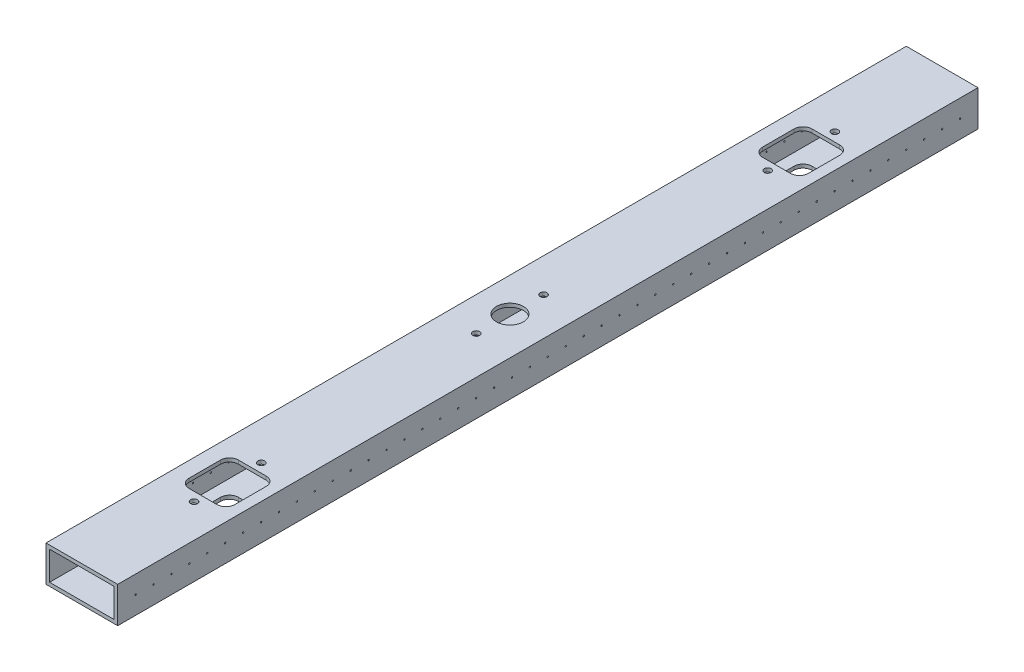
SolidWorks part; units mm, degrees
note: The reader was unsure of these and kept them because the rebuilt part matched: shared geometry of "Sketch2<9>".
ref_plane "Front Plane" through (0, 0, 0) normal (0, 0, 1) x (1, 0, 0)
ref_plane "Top Plane" through (0, 0, 0) normal (0, 1, 0) x (1, 0, 0)
ref_plane "Right Plane" through (0, 0, 0) normal (1, 0, 0) x (0, 0, -1)
sketch "Sketch1" plane through (0, 0, 0) normal (0, 0, 1) x (1, 0, 0)
  line L0 (2.54, -2.54) -> (2.54, -22.86)
  line L1 (0, 0) -> (50.8, 0)
  line L2 (0, 0) -> (0, -25.4)
  line L3 (0, -25.4) -> (50.8, -25.4)
  line L4 (50.8, 0) -> (50.8, -25.4)
  line L5 (2.54, -22.86) -> (48.26, -22.86)
  line L6 (48.26, -2.54) -> (48.26, -22.86)
  line L7 (2.54, -2.54) -> (48.26, -2.54)
  dimension "D1" = 50.8
  dimension "D2" = 25.4
  dimension "D3" = 2.54
extrude "Boss-Extrude1" add sketch "Sketch1" along normal blind 609.6
sketch "Sketch2" plane through (0, 0, 0) normal (0, 1, 0) x (1, 0, 0)
  line L0 (27.124, 0) -> (27.124, -609.6) construction
  line L1 (50.8, 0) -> (0, 0) construction
  line L4 (17.2846, -84.1375) -> (36.9634, -84.1375)
  line L5 (10.9346, -90.4875) -> (10.9346, -112.7125)
  line L6 (17.2846, -119.0625) -> (36.9634, -119.0625)
  line L7 (43.3134, -90.4875) -> (43.3134, -112.7125)
  line L8 (10.9346, -84.1375) -> (43.3134, -119.0625) construction
  line L9 (10.9346, -119.0625) -> (43.3134, -84.1375) construction
  line L13 (10.9346, -496.8875) -> (10.9346, -519.1125)
  line L14 (17.2846, -490.5375) -> (36.9634, -490.5375)
  line L15 (43.3134, -496.8875) -> (43.3134, -519.1125)
  line L16 (17.2846, -525.4625) -> (36.9634, -525.4625)
  line L17 (10.9346, -293.6875) -> (10.9346, -315.9125) [skipped]
  line L18 (17.2846, -322.2625) -> (36.9634, -322.2625) [skipped]
  line L19 (43.3134, -293.6875) -> (43.3134, -315.9125) [skipped]
  line L20 (17.2846, -287.3375) -> (36.9634, -287.3375) [skipped]
  line L21 (50.8, -609.6) -> (50.8, 0) construction
  line L22 (23.949, -280.9875) -> (23.949, -328.6125) construction
  circle A5 centre (27.124, -101.6) radius 23.8125 construction
  circle A6 centre (27.124, -77.7875) radius 2.413
  circle A7 centre (27.124, -125.4125) radius 2.413
  circle A9 centre (23.949, -304.8) radius 23.8125 construction
  circle A11 centre (27.124, -531.8125) radius 2.413
  circle A12 centre (27.124, -508) radius 23.8125 construction
  circle A13 centre (27.124, -484.1875) radius 2.413
  arc A14 (17.2846, -84.1375) -> (10.9346, -90.4875) centre (17.2846, -90.4875) ccw
  arc A15 (10.9346, -112.7125) -> (17.2846, -119.0625) centre (17.2846, -112.7125) ccw
  arc A16 (36.9634, -119.0625) -> (43.3134, -112.7125) centre (36.9634, -112.7125) ccw
  arc A17 (36.9634, -84.1375) -> (43.3134, -90.4875) centre (36.9634, -90.4875) cw
  arc A22 (10.9346, -519.1125) -> (17.2846, -525.4625) centre (17.2846, -519.1125) ccw
  arc A23 (17.2846, -490.5375) -> (10.9346, -496.8875) centre (17.2846, -496.8875) ccw
  arc A24 (36.9634, -490.5375) -> (43.3134, -496.8875) centre (36.9634, -496.8875) cw
  arc A25 (36.9634, -525.4625) -> (43.3134, -519.1125) centre (36.9634, -519.1125) ccw
  arc A26 (10.9346, -315.9125) -> (17.2846, -322.2625) centre (17.2846, -315.9125) ccw [skipped]
  arc A27 (36.9634, -322.2625) -> (43.3134, -315.9125) centre (36.9634, -315.9125) ccw [skipped]
  arc A28 (36.9634, -287.3375) -> (43.3134, -293.6875) centre (36.9634, -293.6875) cw [skipped]
  arc A29 (17.2846, -287.3375) -> (10.9346, -293.6875) centre (17.2846, -293.6875) ccw [skipped]
  circle A31 centre (23.949, -304.8) radius 9.525
  circle A32 centre (27.124, -304.8) radius 23.8125 construction
  circle A33 centre (27.124, -328.6125) radius 2.413 [skipped]
  circle A34 centre (27.124, -280.9875) radius 2.413 [skipped]
  circle A35 centre (23.949, -280.9875) radius 2.413
  circle A36 centre (23.949, -328.6125) radius 2.413
  point P23 (0, 0)
  point P44 (0, 0)
  dimension "D1" = 47.625
  dimension "D3" = 3
  dimension "D5" = 47.625
  dimension "D8" = 3
  dimension "D9" = 34.925
  dimension "D6" = 4.826
  dimension "D7" = 4.826
  dimension "D10" = 6.35
  dimension "D4" = 19.05
  dimension "D11" = 4.826
  dimension "D12" = 26.851
  dimension "0.19" = 4.826
  dimension "D13" = 304.8
  dimension "D2" = 101.6
  dimension "D14" = 3.175
extrude "Cut-Extrude1" cut sketch "Sketch2" against normal through all contours L5 A15 L6 L0 L4 A14 | A17 L4 L0 L6 A16 L7 | L0 A6 | L0 A6 | L0 A7 | L0 A7
extrude "Cut-Extrude2" cut sketch "Sketch2<9>" against normal through all contours L0 A31 | L0 A31 | A35 | A36 | L14 A23 L13 A22 L16 L0 | L16 A25 L15 A24 L14 L0 | L0 A13 | L0 A13 | L0 A11 | L0 A11
sketch "Sketch2<9>" plane through (0, 0, 0) normal (0, 1, 0) x (1, 0, 0) same geometry as "Sketch2"
sketch "Sketch3" plane through (0, 0, 0) normal (0, 1, 0) x (1, 0, 0)
  line L0 (0, -609.6) -> (0, 0) construction
  line L1 (50.8, -304.8) -> (0, -304.8)
  line L2 (50.8, -609.6) -> (50.8, 0) construction
  circle A0 centre (22.225, -355.6) radius 4.7625
  circle A1 centre (22.225, -254) radius 4.7625
  point P8 (25.4, -304.8)
  dimension "D3" = 9.525
  dimension "D1" = 22.225
  dimension "D2" = 50.8
sketch "Sketch4" plane through (0, 0, 0) normal (0, 1, 0) x (1, 0, 0)
  line L0 (25.4, 0) -> (25.4, -609.6)
  line L1 (50.8, 0) -> (0, 0) construction
  line L2 (50.8, -609.6) -> (0, -609.6) construction
  line L3 (43.3134, -101.6) -> (10.9346, -101.6)
  line L4 (43.3134, -90.4875) -> (43.3134, -112.7125) construction
  line L5 (10.9346, -90.4875) -> (10.9346, -112.7125) construction
  line L6 (33.474, -304.8) -> (14.424, -304.8)
  circle A0 centre (25.4, -57.1834) radius 2.6
  circle A1 centre (25.4, -146.0166) radius 2.6
  circle A2 centre (23.949, -304.8) radius 9.525 construction
  circle A3 centre (25.4, -552.4166) radius 2.6
  circle A4 centre (25.4, -463.5834) radius 2.6
  point P12 (27.124, -101.6)
  dimension "D1" = 5.2
  dimension "D3" = 5.2
  dimension "1.75" = 44.45
  dimension "D4" = 44.45
sketch "Sketch5" plane through (50.8, 0, 0) normal (1, 0, 0) x (0, 0, -1)
  line L0 (0, -12.7) -> (-609.6, -12.7) construction
  line L1 (0, -25.4) -> (0, 0) construction
  line L2 (-609.6, -25.4) -> (-609.6, 0) construction
  circle A0 centre (-12.7, -12.7) radius 0.5
  circle A1 centre (-25.4, -12.7) radius 0.5
  circle A2 centre (-38.1, -12.7) radius 0.5
  circle A3 centre (-50.8, -12.7) radius 0.5
  circle A4 centre (-63.5, -12.7) radius 0.5
  circle A5 centre (-76.2, -12.7) radius 0.5
  circle A6 centre (-88.9, -12.7) radius 0.5
  circle A7 centre (-101.6, -12.7) radius 0.5
  circle A8 centre (-114.3, -12.7) radius 0.5
  circle A9 centre (-127, -12.7) radius 0.5
  circle A10 centre (-139.7, -12.7) radius 0.5
  circle A11 centre (-152.4, -12.7) radius 0.5
  circle A12 centre (-165.1, -12.7) radius 0.5
  circle A13 centre (-177.8, -12.7) radius 0.5
  circle A14 centre (-190.5, -12.7) radius 0.5
  circle A15 centre (-203.2, -12.7) radius 0.5
  circle A16 centre (-215.9, -12.7) radius 0.5
  circle A17 centre (-228.6, -12.7) radius 0.5
  circle A18 centre (-241.3, -12.7) radius 0.5
  circle A19 centre (-254, -12.7) radius 0.5
  circle A20 centre (-266.7, -12.7) radius 0.5
  circle A21 centre (-279.4, -12.7) radius 0.5
  circle A22 centre (-292.1, -12.7) radius 0.5
  circle A23 centre (-304.8, -12.7) radius 0.5
  circle A24 centre (-317.5, -12.7) radius 0.5
  circle A25 centre (-330.2, -12.7) radius 0.5
  circle A26 centre (-342.9, -12.7) radius 0.5
  circle A27 centre (-355.6, -12.7) radius 0.5
  circle A28 centre (-368.3, -12.7) radius 0.5
  circle A29 centre (-381, -12.7) radius 0.5
  circle A30 centre (-393.7, -12.7) radius 0.5
  circle A31 centre (-406.4, -12.7) radius 0.5
  circle A32 centre (-419.1, -12.7) radius 0.5
  circle A33 centre (-431.8, -12.7) radius 0.5
  circle A34 centre (-444.5, -12.7) radius 0.5
  circle A35 centre (-457.2, -12.7) radius 0.5
  circle A36 centre (-469.9, -12.7) radius 0.5
  circle A37 centre (-482.6, -12.7) radius 0.5
  circle A38 centre (-495.3, -12.7) radius 0.5
  circle A39 centre (-508, -12.7) radius 0.5
  circle A40 centre (-520.7, -12.7) radius 0.5
  circle A41 centre (-533.4, -12.7) radius 0.5
  circle A42 centre (-546.1, -12.7) radius 0.5
  circle A43 centre (-558.8, -12.7) radius 0.5
  circle A44 centre (-571.5, -12.7) radius 0.5
  circle A45 centre (-584.2, -12.7) radius 0.5
  circle A46 centre (-596.9, -12.7) radius 0.5
  dimension "D1" = 1
  dimension "D2" = 12.7
  dimension "D3" = 47
extrude "Cut-Extrude5" cut sketch "Sketch5" against normal blind 143.002
sketch "Sketch6" plane through (0, 0, 0) normal (0, 1, 0) x (1, 0, 0)
  line L0 (23.949, -280.9875) -> (23.949, -328.6125) construction
  line L1 (25.4, 0) -> (25.4, -609.6) construction
  line L2 (50.8, 0) -> (0, 0) construction
  line L3 (50.8, -609.6) -> (0, -609.6) construction
  circle A0 centre (23.949, -280.9875) radius 2.413 construction
  circle A1 centre (23.949, -328.6125) radius 2.413 construction
